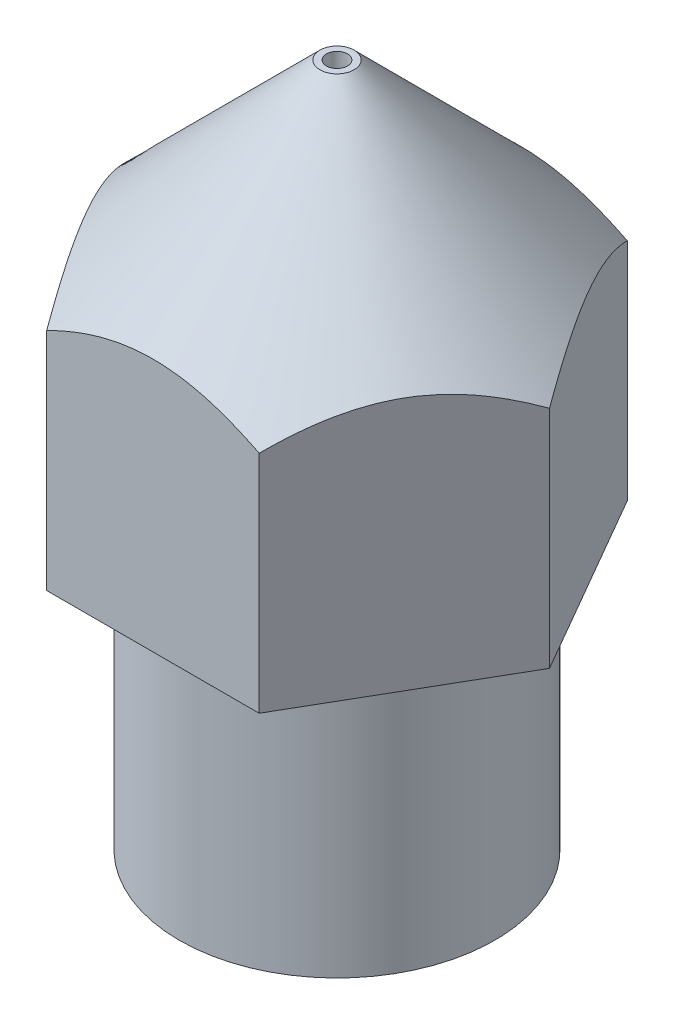
SolidWorks part; units mm, degrees
ref_plane "前基準面" through (0, 0, 0) normal (0, 0, 1) x (1, 0, 0)
ref_plane "上基準面" through (0, 0, 0) normal (0, 1, 0) x (1, 0, 0)
ref_plane "右基準面" through (0, 0, 0) normal (1, 0, 0) x (0, 0, -1)
sketch "草圖1" plane through (0, 0, 0) normal (0, 1, 0) x (1, 0, 0)
  line L1 (2020.7259, -3500) -> (4041.4519, 0)
  line L2 (4041.4519, 0) -> (2020.7259, 3500)
  line L3 (2020.7259, 3500) -> (-2020.7259, 3500)
  line L4 (-2020.7259, 3500) -> (-4041.4519, 0)
  line L5 (-4041.4519, 0) -> (-2020.7259, -3500)
  line L6 (-2020.7259, -3500) -> (2020.7259, -3500)
  circle A0 centre (0, 0) radius 3500 construction
  dimension "D1" = 7000
extrude "填料-伸長1" add sketch "草圖1" along normal blind 8000
sketch "草圖2" plane through (0, 0, 0) normal (0, 0, 1) x (1, 0, 0)
  line L0 (0, 8167.684) -> (0, -355.9358) construction
  line L1 (325, 8000) -> (5325, 3000)
  line L2 (-2020.7259, 8000) -> (2020.7259, 8000) construction
  line L3 (5325, 3000) -> (5325, 8000)
  line L4 (5325, 8000) -> (325, 8000)
  dimension "D1" = 135
  dimension "D2" = 5000
  dimension "D3" = 325
revolve "除料-旋轉1" cut sketch "草圖2" angle 360 about L0
sketch "草圖3" plane through (0, 8000, 0) normal (0, 1, 0) x (1, 0, 0)
  circle A0 centre (0, 0) radius 200
  dimension "D1" = 400
extrude "除料-伸長1" cut sketch "草圖3" against normal blind 8000
sketch "草圖4" plane through (0, 0, 0) normal (0, -1, 0) x (1, 0, 0)
  circle A0 centre (0, 0) radius 1190
  dimension "D1" = 2380
extrude "除料-伸長2" cut sketch "草圖4" against normal blind 6000
chamfer "導角3" distance 1000 angle 45 1 edges at (0, 6000, -200)
sketch "草圖5" plane through (0, 0, 0) normal (0, -1, 0) x (1, 0, 0)
  circle A0 centre (0, 0) radius 3000
  circle A1 centre (0, 0) radius 1190
  dimension "D1" = 6000
  dimension "D2" = 2380
extrude "填料-伸長2" add sketch "草圖5" along normal blind 5000
cosmetic thread "裝飾螺紋線3" parameters "D2"=5999
sketch "草圖6" plane through (0, 0, -3500) normal (0, 0, -1) x (-1, 0, 0)
  line L0 (-952.7912, 1168.2245) -> (1395.1586, 1168.2245) construction
  text T0 "4" font "Century Gothic" height 3000
extrude "除料-伸長3" cut sketch "草圖6" against normal blind 100
